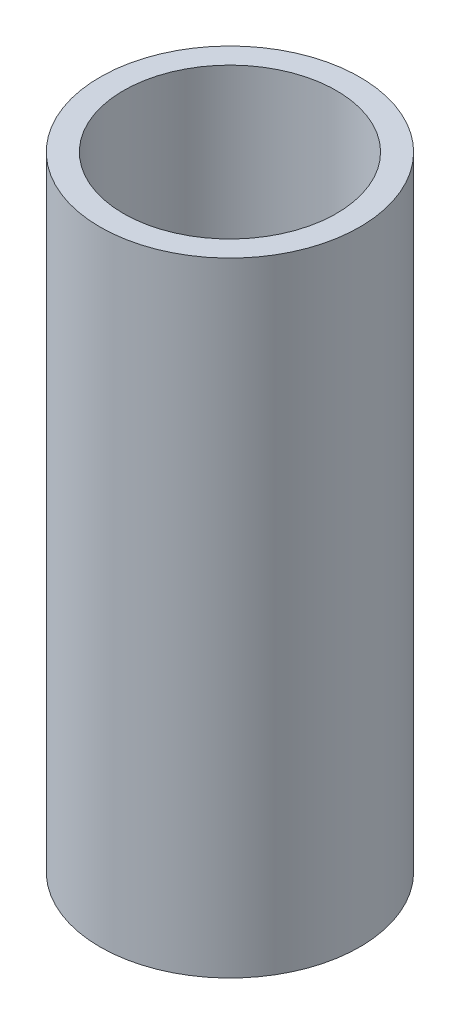
SolidWorks part; units mm, degrees
ref_plane "Front Plane" through (0, 0, 0) normal (0, 0, 1) x (1, 0, 0)
ref_plane "Top Plane" through (0, 0, 0) normal (0, 1, 0) x (1, 0, 0)
ref_plane "Right Plane" through (0, 0, 0) normal (1, 0, 0) x (0, 0, -1)
sketch "Sketch1" plane through (0, 0, 0) normal (0, 1, 0) x (1, 0, 0)
  circle A0 centre (0, 0) radius 3.075
  circle A1 centre (0, 0) radius 3.75
  dimension "D1" = 6.15
  dimension "D2" = 7.5
extrude "Boss-Extrude1" add sketch "Sketch1" along normal blind 18
